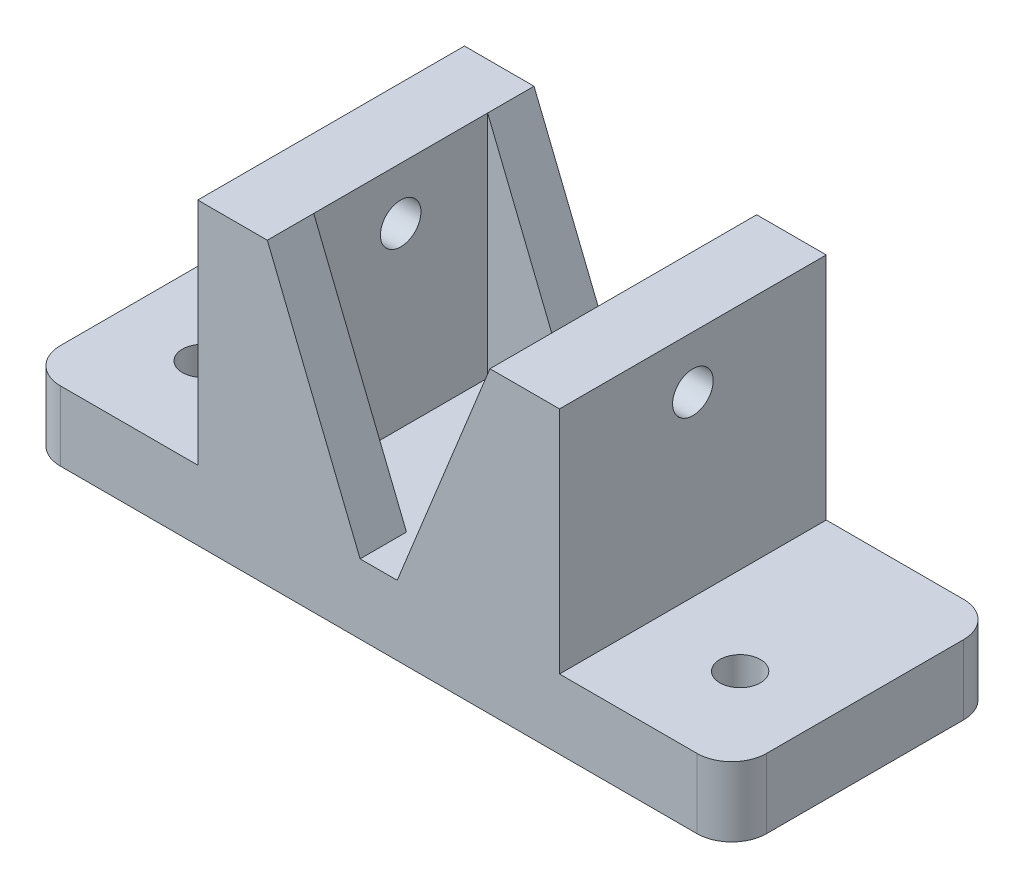
SolidWorks part; units mm, degrees
ref_plane "Front Plane" through (0, 0, 0) normal (0, 0, 1) x (1, 0, 0)
ref_plane "Top Plane" through (0, 0, 0) normal (0, 1, 0) x (1, 0, 0)
ref_plane "Right Plane" through (0, 0, 0) normal (1, 0, 0) x (0, 0, -1)
sketch "Sketch1" plane through (0, 0, 0) normal (0, 1, 0) x (1, 0, 0)
  line L0 (23.175, 0) -> (-23.175, 0) construction
  line L1 (0, 15) -> (0, -8) construction
  line L2 (-27.452, -8) -> (27.452, -8)
  line L3 (-30.452, -5) -> (-30.452, 12)
  line L4 (-27.452, 15) -> (27.452, 15)
  line L5 (30.452, -5) -> (30.452, 12)
  circle A0 centre (-23.175, 0) radius 1.75
  circle A1 centre (23.175, 0) radius 1.75
  arc A2 (27.452, -8) -> (30.452, -5) centre (27.452, -5) ccw
  arc A3 (27.452, 15) -> (30.452, 12) centre (27.452, 12) cw
  arc A4 (-27.452, -8) -> (-30.452, -5) centre (-27.452, -5) cw
  arc A5 (-30.452, 12) -> (-27.452, 15) centre (-27.452, 12) cw
  dimension "D1" = 3.5
  dimension "D2" = 3.5
  dimension "D6" = 3
  dimension "D3" = 46.35
  dimension "D4" = 8
  dimension "D5" = 15
extrude "Boss-Extrude1" add sketch "Sketch1" along normal blind 6
sketch "Sketch2" plane through (0, 6, 0) normal (0, 1, 0) x (1, 0, 0)
  line L0 (27.452, 15) -> (-27.452, 15) construction
  line L1 (9.6, 15) -> (15.6, 15)
  line L2 (9.6, 15) -> (9.6, -8)
  line L3 (9.6, -8) -> (15.6, -8)
  line L4 (15.6, 15) -> (15.6, -8)
  line L5 (-27.452, -8) -> (27.452, -8) construction
  line L6 (0, -8) -> (0, 20.4318) construction
  line L7 (-9.6, -8) -> (-15.6, -8)
  line L8 (-15.6, 15) -> (-15.6, -8)
  line L9 (-9.6, 15) -> (-15.6, 15)
  line L10 (-9.6, 15) -> (-9.6, -8)
  dimension "D1" = 6
  dimension "D2" = 31.2
extrude "Boss-Extrude2" add sketch "Sketch2" along normal blind 19.8
sketch "Sketch3" plane through (-15.6, 0, 0) normal (-1, 0, 0) x (0, 0, 1)
  line L0 (-15, 25.8) -> (8, 25.8) construction
  circle A0 centre (-3.5, 21.3) radius 1.75
  dimension "D1" = 3.5
  dimension "D2" = 4.5
extrude "Cut-Extrude1" cut sketch "Sketch3" against normal blind 40.8
sketch "Sketch4" plane through (0, 6, 0) normal (0, 1, 0) x (1, 0, 0)
  line L0 (30.452, 3.5) -> (-40.9498, 3.5) construction
  line L1 (9.6, 15) -> (1.6, 15)
  line L2 (9.6, 15) -> (9.6, 11)
  line L3 (9.6, 11) -> (1.6, 11)
  line L4 (1.6, 15) -> (1.6, 11)
  line L5 (30.452, -5) -> (30.452, 12) construction
  line L6 (0, -8) -> (0, 22.6894) construction
  line L7 (-9.6, -8) -> (9.6, -8) construction
  line L8 (-9.6, 11) -> (-1.6, 11)
  line L9 (-1.6, 15) -> (-1.6, 11)
  line L10 (-9.6, 15) -> (-1.6, 15)
  line L11 (-9.6, 15) -> (-9.6, 11)
  line L12 (-9.6, -8) -> (-9.6, -4)
  line L13 (-9.6, -8) -> (-1.6, -8)
  line L14 (-1.6, -8) -> (-1.6, -4)
  line L15 (-9.6, -4) -> (-1.6, -4)
  line L16 (9.6, -4) -> (1.6, -4)
  line L17 (1.6, -8) -> (1.6, -4)
  line L18 (9.6, -8) -> (1.6, -8)
  line L19 (9.6, -8) -> (9.6, -4)
  dimension "D1" = 4
  dimension "D2" = 8
extrude "Boss-Extrude3" add sketch "Sketch4" along normal blind 19.8
sketch "Sketch5" plane through (0, 0, -15) normal (0, 0, -1) x (-1, 0, 0)
  line L0 (-1.6, 6) -> (-9.6, 25.8)
  line L1 (-15.6, 25.8) -> (-1.6, 25.8) construction
  line L4 (0, 0) -> (0, 29.3135) construction
  line L6 (1.6, 6) -> (9.6, 25.8)
  line L8 (-9.6, 25.8) -> (-1.6, 25.8)
  line L9 (-1.6, 25.8) -> (-1.6, 6)
  line L10 (1.6, 6) -> (1.6, 25.8)
  line L11 (1.6, 25.8) -> (9.6, 25.8)
extrude "Cut-Extrude3" cut sketch "Sketch5" against normal blind 93.8
